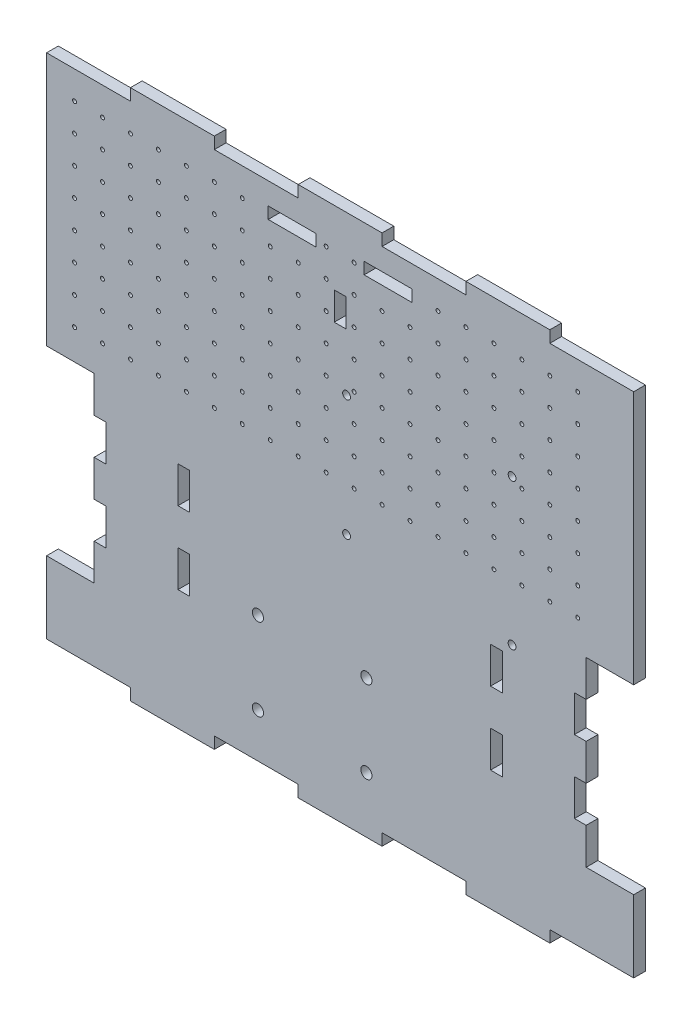
SolidWorks part; units mm, degrees
ref_plane "Front Plane" through (0, 0, 0) normal (0, 0, 1) x (1, 0, 0)
ref_plane "Top Plane" through (0, 0, 0) normal (0, 1, 0) x (1, 0, 0)
ref_plane "Right Plane" through (0, 0, 0) normal (1, 0, 0) x (0, 0, -1)
sketch "Sketch1" plane through (0, 0, 0) normal (0, 0, 1) x (1, 0, 0)
  line L1 (-133.35, 120.65) -> (133.35, 120.65)
  line L2 (-133.35, 120.65) -> (-133.35, -120.65)
  line L3 (-133.35, -120.65) -> (133.35, -120.65)
  line L4 (133.35, 120.65) -> (133.35, -120.65)
  line L5 (-133.35, 120.65) -> (133.35, -120.65) construction
  line L6 (-133.35, -120.65) -> (133.35, 120.65) construction
  point P0 (0, 0)
  dimension "D1" = 241.3
  dimension "D2" = 266.7
extrude "Boss-Extrude1" add sketch "Sketch1" along normal blind 5.334
sketch "Sketch2" plane through (0, 0, 0) normal (0, 0, -1) x (-1, 0, 0)
  line L0 (133.35, 120.65) -> (133.35, -120.65) construction
  line L1 (133.35, 0) -> (111.76, 0)
  line L2 (133.35, 0) -> (133.35, -82.55)
  line L3 (133.35, -82.55) -> (111.76, -82.55)
  line L4 (111.76, 0) -> (111.76, -82.55)
  line L5 (-133.35, -120.65) -> (-133.35, 120.65) construction
  line L6 (-133.35, 0) -> (-111.76, 0)
  line L7 (-133.35, 0) -> (-133.35, -82.55)
  line L8 (-133.35, -82.55) -> (-111.76, -82.55)
  line L9 (-111.76, 0) -> (-111.76, -82.55)
  line L10 (133.35, -120.65) -> (-133.35, -120.65) construction
  dimension "D1" = 82.55
  dimension "D2" = 82.55
  dimension "D3" = 38.1
  dimension "D4" = 38.1
  dimension "D5" = 21.59
  dimension "D6" = 21.59
extrude "Cut-Extrude1" cut sketch "Sketch2" against normal through all
sketch "Sketch9" plane through (0, 0, 5.334) normal (0, 0, 1) x (1, 0, 0)
  line L0 (-111.76, 0) -> (-111.76, -82.55) construction
  line L1 (-111.76, -16.51) -> (-106.426, -16.51)
  line L2 (-111.76, -16.51) -> (-111.76, -33.02)
  line L3 (-111.76, -33.02) -> (-106.426, -33.02)
  line L4 (-106.426, -16.51) -> (-106.426, -33.02)
  line L5 (-111.76, 0) -> (-106.426, 0) construction
  line L6 (-111.76, -49.53) -> (-106.426, -49.53)
  line L7 (-111.76, -49.53) -> (-111.76, -66.04)
  line L8 (-111.76, -66.04) -> (-106.426, -66.04)
  line L9 (-106.426, -49.53) -> (-106.426, -66.04)
  line L10 (-106.426, 0) -> (-106.426, -16.51) construction
  line L11 (-106.426, -33.02) -> (-106.426, -49.53) construction
  line L12 (-111.76, -82.55) -> (-106.426, -82.55) construction
  line L13 (-106.426, -82.55) -> (-106.426, -66.04) construction
  line L14 (0, -120.65) -> (0, 120.65) construction
  line L15 (-133.35, -120.65) -> (133.35, -120.65) construction
  line L16 (133.35, 120.65) -> (-133.35, 120.65) construction
  line L17 (106.426, -82.55) -> (106.426, -66.04) construction
  line L18 (111.76, -82.55) -> (106.426, -82.55) construction
  line L19 (106.426, -33.02) -> (106.426, -49.53) construction
  line L20 (106.426, 0) -> (106.426, -16.51) construction
  line L21 (111.76, 0) -> (106.426, 0) construction
  line L22 (106.426, -49.53) -> (106.426, -66.04)
  line L23 (111.76, -66.04) -> (106.426, -66.04)
  line L24 (111.76, -49.53) -> (111.76, -66.04)
  line L25 (111.76, -49.53) -> (106.426, -49.53)
  line L26 (106.426, -16.51) -> (106.426, -33.02)
  line L27 (111.76, -33.02) -> (106.426, -33.02)
  line L28 (111.76, -16.51) -> (111.76, -33.02)
  line L29 (111.76, -16.51) -> (106.426, -16.51)
  dimension "D1" = 5.334
extrude "Cut-Extrude2" cut sketch "Sketch9" against normal through all
sketch "Sketch10" plane through (0, 0, 5.334) normal (0, 0, 1) x (1, 0, 0)
  line L2 (-133.35, -120.65) -> (133.35, -120.65) construction
  line L3 (-133.35, -82.55) -> (-133.35, -120.65) construction
  circle A0 centre (-37.338, -95.25) radius 2.54
  circle A1 centre (11.938, -95.25) radius 2.54
  circle A2 centre (11.938, -57.912) radius 2.54
  circle A3 centre (-37.338, -57.912) radius 2.54
  dimension "D1" = 96.012
  dimension "D2" = 49.276
  dimension "D3" = 25.4
  dimension "D4" = 2
  dimension "D5" = 2
extrude "Cut-Extrude3" cut sketch "Sketch10" against normal through all
sketch "Sketch19" plane through (0, 0, 5.334) normal (0, 0, 1) x (1, 0, 0)
  line L0 (-10.8958, 100.076) -> (10.8958, 100.076) construction
  line L1 (-32.6875, 105.41) -> (-10.8958, 105.41)
  line L2 (-32.6875, 105.41) -> (-32.6875, 100.076)
  line L3 (-32.6875, 100.076) -> (-10.8958, 100.076)
  line L4 (-10.8958, 105.41) -> (-10.8958, 100.076)
  line L5 (10.8958, 105.41) -> (32.6875, 105.41)
  line L6 (10.8958, 105.41) -> (10.8958, 100.076)
  line L7 (10.8958, 100.076) -> (32.6875, 100.076)
  line L8 (32.6875, 105.41) -> (32.6875, 100.076)
  line L9 (-32.6875, 100.076) -> (-133.35, 100.076) construction
  line L10 (-133.35, 120.65) -> (-133.35, 0) construction
  line L11 (32.6875, 100.076) -> (133.35, 100.076) construction
  line L12 (133.35, 0) -> (133.35, 120.65) construction
  line L13 (133.35, 120.65) -> (-133.35, 120.65) construction
  dimension "D1" = 15.24
  dimension "D2" = 5.334
  dimension "D3" = 5.334
  dimension "D4" = 21.7917
sketch "Sketch23" plane through (0, 0, 5.334) normal (0, 0, 1) x (1, 0, 0)
  line L0 (-106.426, -24.765) -> (-61.976, -24.765) construction
  line L1 (-106.426, -33.02) -> (-106.426, -16.51) construction
  line L2 (-106.426, -16.51) -> (-68.326, -16.51) construction
  line L3 (-106.426, -33.02) -> (-68.326, -33.02) construction
  line L4 (-111.76, -41.275) -> (111.76, -41.275) construction
  line L5 (-111.76, -33.02) -> (-111.76, -49.53) construction
  line L6 (111.76, -49.53) -> (111.76, -33.02) construction
  line L7 (-106.426, -49.53) -> (-68.326, -49.53) construction
  line L8 (-106.426, -57.785) -> (-61.976, -57.785) construction
  line L9 (-106.426, -66.04) -> (-68.326, -66.04) construction
  line L10 (0, -120.65) -> (0, 120.65) construction
  line L11 (-133.35, -120.65) -> (133.35, -120.65) construction
  line L12 (133.35, 120.65) -> (-133.35, 120.65) construction
  line L13 (106.426, -66.04) -> (68.326, -66.04) construction
  line L14 (106.426, -49.53) -> (68.326, -49.53) construction
  line L15 (106.426, -33.02) -> (68.326, -33.02) construction
  line L16 (106.426, -16.51) -> (68.326, -16.51) construction
  line L17 (-68.326, -66.04) -> (-73.66, -66.04)
  line L18 (68.326, -16.51) -> (73.66, -16.51)
  line L19 (68.326, -16.51) -> (68.326, -33.02)
  line L20 (68.326, -33.02) -> (73.66, -33.02)
  line L21 (73.66, -16.51) -> (73.66, -33.02)
  line L22 (68.326, -49.53) -> (73.66, -49.53)
  line L23 (68.326, -49.53) -> (68.326, -66.04)
  line L24 (68.326, -66.04) -> (73.66, -66.04)
  line L25 (73.66, -49.53) -> (73.66, -66.04)
  line L26 (-73.66, -49.53) -> (-73.66, -66.04)
  line L27 (-68.326, -49.53) -> (-68.326, -66.04)
  line L28 (-68.326, -49.53) -> (-73.66, -49.53)
  line L29 (-68.326, -33.02) -> (-73.66, -33.02)
  line L30 (-73.66, -16.51) -> (-73.66, -33.02)
  line L31 (-68.326, -16.51) -> (-73.66, -16.51)
  line L32 (-68.326, -16.51) -> (-68.326, -33.02)
  line L33 (106.426, -16.51) -> (106.426, -33.02) construction
  dimension "D1" = 5.334
  dimension "D2" = 5.334
  dimension "D3" = 32.766
  dimension "D4" = 32.766
extrude "Cut-Extrude8" cut sketch "Sketch23" against normal through all
extrude "Cut-Extrude9" cut sketch "Sketch19" against normal through all contours L1 L4 L3 L2
sketch "Sketch24" plane through (0, 0, 0) normal (0, 0, -1) x (-1, 0, 0)
  line L0 (0, 120.65) -> (0, -120.65) construction
  line L1 (-133.35, 120.65) -> (133.35, 120.65) construction
  line L2 (133.35, -120.65) -> (-133.35, -120.65) construction
extrude "Cut-Extrude11" cut sketch "Sketch19<5>" against normal through all
sketch "Sketch19<5>" plane through (0, 0, 5.334) normal (0, 0, 1) x (1, 0, 0) same geometry as "Sketch19"
sketch "Sketch26" plane through (0, 0, 5.334) normal (0, 0, 1) x (1, 0, 0)
sketch "Sketch27" plane through (0, 0, 5.334) normal (0, 0, 1) x (1, 0, 0)
  line L0 (10.8958, 100.076) -> (32.6875, 100.076) construction
  line L1 (-2.667, 87.376) -> (2.667, 87.376)
  line L2 (-2.667, 87.376) -> (-2.667, 74.676)
  line L3 (-2.667, 74.676) -> (2.667, 74.676)
  line L4 (2.667, 87.376) -> (2.667, 74.676)
  line L9 (133.35, 0) -> (133.35, 120.65) construction
  line L10 (-133.35, 120.65) -> (-133.35, 0) construction
  line L11 (2.667, 74.676) -> (133.35, 74.676) construction
  line L12 (-2.667, 74.676) -> (-133.35, 74.676) construction
  dimension "D1" = 12.7
  dimension "D4" = 12.7
  dimension "D5" = 5.334
extrude "Cut-Extrude12" cut sketch "Sketch27" against normal through all
sketch "Sketch28" plane through (0, 0, 0) normal (0, 0, -1) x (-1, 0, 0)
  line L0 (133.35, -120.65) -> (-133.35, -120.65) construction
  line L1 (-133.35, -120.65) -> (-95.25, -120.65)
  line L2 (-133.35, -120.65) -> (-133.35, -115.316)
  line L3 (-133.35, -115.316) -> (-95.25, -115.316)
  line L4 (-95.25, -120.65) -> (-95.25, -115.316)
  line L5 (-57.15, -120.65) -> (-19.05, -120.65)
  line L6 (-57.15, -120.65) -> (-57.15, -115.316)
  line L7 (-57.15, -115.316) -> (-19.05, -115.316)
  line L8 (-19.05, -120.65) -> (-19.05, -115.316)
  line L9 (133.35, -82.55) -> (133.35, -120.65) construction
  line L10 (19.05, -120.65) -> (57.15, -120.65)
  line L11 (19.05, -120.65) -> (19.05, -115.316)
  line L12 (19.05, -115.316) -> (57.15, -115.316)
  line L13 (57.15, -120.65) -> (57.15, -115.316)
  line L14 (95.25, -120.65) -> (133.35, -120.65)
  line L16 (95.25, -115.316) -> (133.35, -115.316)
  line L17 (133.35, -120.65) -> (133.35, -115.316)
  line L18 (-95.25, -115.316) -> (-57.15, -115.316) construction
  line L19 (-19.05, -115.316) -> (19.05, -115.316) construction
  line L20 (95.25, -115.316) -> (57.15, -115.316) construction
  line L21 (133.35, 120.65) -> (133.35, -115.316) construction
  line L22 (133.35, -115.316) -> (133.5431, -115.1744) construction
  line L41 (95.25, -120.65) -> (95.25, -115.316)
  dimension "D1" = 5.334
extrude "Cut-Extrude13" cut sketch "Sketch28" against normal through all
sketch "Sketch29" plane through (0, 0, 0) normal (0, 0, -1) x (-1, 0, 0)
  line L0 (-133.35, 120.65) -> (133.35, 120.65) construction
  line L1 (-133.35, 120.65) -> (-95.25, 120.65)
  line L2 (-133.35, 120.65) -> (-133.35, 115.316)
  line L3 (-133.35, 115.316) -> (-95.25, 115.316)
  line L4 (-95.25, 120.65) -> (-95.25, 115.316)
  line L5 (-57.15, 120.65) -> (-19.05, 120.65)
  line L6 (-57.15, 120.65) -> (-57.15, 115.316)
  line L7 (-57.15, 115.316) -> (-19.05, 115.316)
  line L8 (-19.05, 120.65) -> (-19.05, 115.316)
  line L9 (133.35, 120.65) -> (133.35, 0) construction
  line L10 (19.05, 120.65) -> (57.15, 120.65)
  line L11 (19.05, 120.65) -> (19.05, 115.316)
  line L12 (19.05, 115.316) -> (57.15, 115.316)
  line L13 (57.15, 120.65) -> (57.15, 115.316)
  line L14 (95.25, 120.65) -> (133.35, 120.65)
  line L15 (95.25, 120.65) -> (95.25, 115.316)
  line L16 (95.25, 115.316) -> (133.35, 115.316)
  line L17 (133.35, 120.65) -> (133.35, 115.316)
  line L18 (-95.25, 115.316) -> (-57.15, 115.316) construction
  line L19 (19.05, 115.316) -> (-19.05, 115.316) construction
  line L20 (57.15, 115.316) -> (95.25, 115.316) construction
  dimension "D1" = 5.334
extrude "Cut-Extrude14" cut sketch "Sketch29" against normal through all
sketch "Sketch30" plane through (0, 0, 5.334) normal (0, 0, 1) x (1, 0, 0)
  line L0 (-95.25, 115.316) -> (-133.35, 115.316) construction
  line L1 (-133.35, 115.316) -> (-133.35, 0) construction
  line L2 (-120.65, 102.616) -> (-107.95, 102.616) construction
  circle A0 centre (-120.65, 102.616) radius 0.889
  circle A1 centre (-107.95, 102.616) radius 0.889
  circle A2 centre (-95.25, 102.616) radius 0.889
  circle A3 centre (-82.55, 102.616) radius 0.889
  circle A4 centre (-69.85, 102.616) radius 0.889
  circle A5 centre (-57.15, 102.616) radius 0.889
  circle A6 centre (-44.45, 102.616) radius 0.889
  circle A7 centre (-31.75, 102.616) radius 0.889 [skipped]
  circle A8 centre (-19.05, 102.616) radius 0.889 [skipped]
  circle A9 centre (-6.35, 102.616) radius 0.889
  circle A10 centre (6.35, 102.616) radius 0.889
  circle A11 centre (19.05, 102.616) radius 0.889 [skipped]
  circle A12 centre (31.75, 102.616) radius 0.889 [skipped]
  circle A13 centre (44.45, 102.616) radius 0.889
  circle A14 centre (57.15, 102.616) radius 0.889
  circle A15 centre (69.85, 102.616) radius 0.889
  circle A16 centre (82.55, 102.616) radius 0.889
  circle A17 centre (95.25, 102.616) radius 0.889
  circle A18 centre (107.95, 102.616) radius 0.889
  circle A19 centre (-107.95, 89.916) radius 0.889
  circle A20 centre (-95.25, 89.916) radius 0.889
  circle A21 centre (-82.55, 89.916) radius 0.889
  circle A22 centre (-69.85, 89.916) radius 0.889
  circle A23 centre (-57.15, 89.916) radius 0.889
  circle A24 centre (-44.45, 89.916) radius 0.889
  circle A25 centre (-31.75, 89.916) radius 0.889
  circle A26 centre (-19.05, 89.916) radius 0.889
  circle A27 centre (-6.35, 89.916) radius 0.889
  circle A28 centre (6.35, 89.916) radius 0.889
  circle A29 centre (19.05, 89.916) radius 0.889
  circle A30 centre (31.75, 89.916) radius 0.889
  circle A31 centre (44.45, 89.916) radius 0.889
  circle A32 centre (57.15, 89.916) radius 0.889
  circle A33 centre (69.85, 89.916) radius 0.889
  circle A34 centre (82.55, 89.916) radius 0.889
  circle A35 centre (95.25, 89.916) radius 0.889
  circle A36 centre (107.95, 89.916) radius 0.889
  circle A37 centre (-107.95, 77.216) radius 0.889
  circle A38 centre (-95.25, 77.216) radius 0.889
  circle A39 centre (-82.55, 77.216) radius 0.889
  circle A40 centre (-69.85, 77.216) radius 0.889
  circle A41 centre (-57.15, 77.216) radius 0.889
  circle A42 centre (-44.45, 77.216) radius 0.889
  circle A43 centre (-31.75, 77.216) radius 0.889
  circle A44 centre (-19.05, 77.216) radius 0.889
  circle A45 centre (-6.35, 77.216) radius 0.889
  circle A46 centre (6.35, 77.216) radius 0.889
  circle A47 centre (19.05, 77.216) radius 0.889
  circle A48 centre (31.75, 77.216) radius 0.889
  circle A49 centre (44.45, 77.216) radius 0.889
  circle A50 centre (57.15, 77.216) radius 0.889
  circle A51 centre (69.85, 77.216) radius 0.889
  circle A52 centre (82.55, 77.216) radius 0.889
  circle A53 centre (95.25, 77.216) radius 0.889
  circle A54 centre (107.95, 77.216) radius 0.889
  circle A55 centre (-107.95, 64.516) radius 0.889
  circle A56 centre (-95.25, 64.516) radius 0.889
  circle A57 centre (-82.55, 64.516) radius 0.889
  circle A58 centre (-69.85, 64.516) radius 0.889
  circle A59 centre (-57.15, 64.516) radius 0.889
  circle A60 centre (-44.45, 64.516) radius 0.889
  circle A61 centre (-31.75, 64.516) radius 0.889
  circle A62 centre (-19.05, 64.516) radius 0.889
  circle A63 centre (-6.35, 64.516) radius 0.889
  circle A64 centre (6.35, 64.516) radius 0.889
  circle A65 centre (19.05, 64.516) radius 0.889
  circle A66 centre (31.75, 64.516) radius 0.889
  circle A67 centre (44.45, 64.516) radius 0.889
  circle A68 centre (57.15, 64.516) radius 0.889
  circle A69 centre (69.85, 64.516) radius 0.889
  circle A70 centre (82.55, 64.516) radius 0.889
  circle A71 centre (95.25, 64.516) radius 0.889
  circle A72 centre (107.95, 64.516) radius 0.889
  circle A73 centre (-107.95, 51.816) radius 0.889
  circle A74 centre (-95.25, 51.816) radius 0.889
  circle A75 centre (-82.55, 51.816) radius 0.889
  circle A76 centre (-69.85, 51.816) radius 0.889
  circle A77 centre (-57.15, 51.816) radius 0.889
  circle A78 centre (-44.45, 51.816) radius 0.889
  circle A79 centre (-31.75, 51.816) radius 0.889
  circle A80 centre (-19.05, 51.816) radius 0.889
  circle A81 centre (-6.35, 51.816) radius 0.889
  circle A82 centre (6.35, 51.816) radius 0.889
  circle A83 centre (19.05, 51.816) radius 0.889
  circle A84 centre (31.75, 51.816) radius 0.889
  circle A85 centre (44.45, 51.816) radius 0.889
  circle A86 centre (57.15, 51.816) radius 0.889
  circle A87 centre (69.85, 51.816) radius 0.889
  circle A88 centre (82.55, 51.816) radius 0.889
  circle A89 centre (95.25, 51.816) radius 0.889
  circle A90 centre (107.95, 51.816) radius 0.889
  circle A91 centre (-107.95, 39.116) radius 0.889
  circle A92 centre (-95.25, 39.116) radius 0.889
  circle A93 centre (-82.55, 39.116) radius 0.889
  circle A94 centre (-69.85, 39.116) radius 0.889
  circle A95 centre (-57.15, 39.116) radius 0.889
  circle A96 centre (-44.45, 39.116) radius 0.889
  circle A97 centre (-31.75, 39.116) radius 0.889
  circle A98 centre (-19.05, 39.116) radius 0.889
  circle A99 centre (-6.35, 39.116) radius 0.889
  circle A100 centre (6.35, 39.116) radius 0.889
  circle A101 centre (19.05, 39.116) radius 0.889
  circle A102 centre (31.75, 39.116) radius 0.889
  circle A103 centre (44.45, 39.116) radius 0.889
  circle A104 centre (57.15, 39.116) radius 0.889
  circle A105 centre (69.85, 39.116) radius 0.889
  circle A106 centre (82.55, 39.116) radius 0.889
  circle A107 centre (95.25, 39.116) radius 0.889
  circle A108 centre (107.95, 39.116) radius 0.889
  circle A109 centre (-107.95, 26.416) radius 0.889
  circle A110 centre (-95.25, 26.416) radius 0.889
  circle A111 centre (-82.55, 26.416) radius 0.889
  circle A112 centre (-69.85, 26.416) radius 0.889
  circle A113 centre (-57.15, 26.416) radius 0.889
  circle A114 centre (-44.45, 26.416) radius 0.889
  circle A115 centre (-31.75, 26.416) radius 0.889
  circle A116 centre (-19.05, 26.416) radius 0.889
  circle A117 centre (-6.35, 26.416) radius 0.889
  circle A118 centre (6.35, 26.416) radius 0.889
  circle A119 centre (19.05, 26.416) radius 0.889
  circle A120 centre (31.75, 26.416) radius 0.889
  circle A121 centre (44.45, 26.416) radius 0.889
  circle A122 centre (57.15, 26.416) radius 0.889
  circle A123 centre (69.85, 26.416) radius 0.889
  circle A124 centre (82.55, 26.416) radius 0.889
  circle A125 centre (95.25, 26.416) radius 0.889
  circle A126 centre (107.95, 26.416) radius 0.889
  circle A127 centre (-107.95, 13.716) radius 0.889
  circle A128 centre (-95.25, 13.716) radius 0.889
  circle A129 centre (-82.55, 13.716) radius 0.889
  circle A130 centre (-69.85, 13.716) radius 0.889
  circle A131 centre (-57.15, 13.716) radius 0.889
  circle A132 centre (-44.45, 13.716) radius 0.889
  circle A133 centre (-31.75, 13.716) radius 0.889
  circle A134 centre (-19.05, 13.716) radius 0.889
  circle A135 centre (-6.35, 13.716) radius 0.889
  circle A136 centre (6.35, 13.716) radius 0.889
  circle A137 centre (19.05, 13.716) radius 0.889
  circle A138 centre (31.75, 13.716) radius 0.889
  circle A139 centre (44.45, 13.716) radius 0.889
  circle A140 centre (57.15, 13.716) radius 0.889
  circle A141 centre (69.85, 13.716) radius 0.889
  circle A142 centre (82.55, 13.716) radius 0.889
  circle A143 centre (95.25, 13.716) radius 0.889
  circle A144 centre (107.95, 13.716) radius 0.889
  circle A145 centre (-120.65, 89.916) radius 0.889
  circle A146 centre (-120.65, 77.216) radius 0.889
  circle A147 centre (-120.65, 64.516) radius 0.889
  circle A148 centre (-120.65, 51.816) radius 0.889
  circle A149 centre (-120.65, 39.116) radius 0.889
  circle A150 centre (-120.65, 26.416) radius 0.889
  circle A151 centre (-120.65, 13.716) radius 0.889
  dimension "D1" = 1.778
  dimension "D2" = 12.7
  dimension "D3" = 12.7
  dimension "D6" = 12.7
  dimension "D4" = 19
  dimension "D5" = 8
extrude "Cut-Extrude15" cut sketch "Sketch30" against normal through all
sketch "Sketch32" plane through (0, 0, 0) normal (0, 0, -1) x (-1, 0, 0)
  circle A0 centre (-78.105, -11.938) radius 1.778 construction
  circle A1 centre (-2.921, -6.096) radius 1.778 construction
  circle A2 centre (-78.105, 54.356) radius 1.778 construction
  circle A3 centre (-2.921, 48.768) radius 1.778 construction
  circle A4 centre (-78.105, -11.938) radius 1.778
  circle A5 centre (-2.921, -6.096) radius 1.778
  circle A6 centre (-78.105, 54.356) radius 1.778
  circle A7 centre (-2.921, 48.768) radius 1.778
extrude "Cut-Extrude16" cut sketch "Sketch32" against normal through all
equation "\"MDF\"= .21in"
equation "\"Foamcore\"= .13in"
equation "\"Gmaterial\"= \"MDF\""
equation "\"D1@Sketch9\"=\"MDF\""
equation "\"D2@Sketch19\"=\"MDF\""
equation "\"D3@Sketch19\"=\"MDF\""
equation "\"D1@Sketch23\"=\"MDF\""
equation "\"D2@Sketch23\"=\"D1@Sketch23\""
equation "\"D1@Boss-Extrude1\"=\"MDF\""
equation "\"D3@Sketch23\"=1.29"
equation "\"D5@Sketch27\"=\"MDF\""
equation "\"D1@Sketch28\"=\"MDF\""
equation "\"D1@Sketch29\"=\"MDF\""
